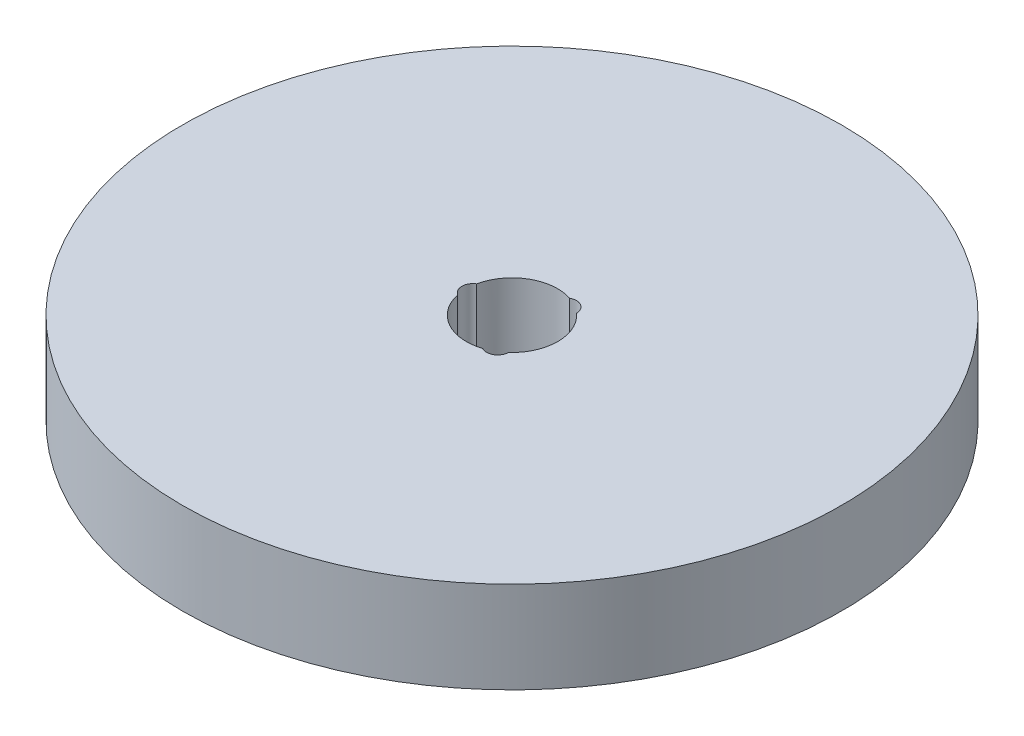
SolidWorks part; units mm, degrees
ref_plane "Front Plane" through (0, 0, 0) normal (0, 0, 1) x (1, 0, 0)
ref_plane "Top Plane" through (0, 0, 0) normal (0, 1, 0) x (1, 0, 0)
ref_plane "Right Plane" through (0, 0, 0) normal (1, 0, 0) x (0, 0, -1)
sketch "Sketch1" plane through (0, 0, 0) normal (0, 1, 0) x (1, 0, 0)
  circle A0 centre (0, 0) radius 90
  dimension "FLANGE_OD" = 180
extrude "Boss-Extrude1" add sketch "Sketch1" along normal blind 25
sketch "Sketch2" plane through (0, 0, 0) normal (0, 1, 0) x (1, 0, 0)
  circle A0 centre (0, 0) radius 12.5
  dimension "BORE_D" = 25
extrude "Cut-Extrude1" cut sketch "Sketch2" along normal through all
sketch "Sketch3" plane through (0, 25, 0) normal (0, 1, 0) x (1, 0, 0)
  circle A0 centre (0, 0) radius 10.6513 construction
  circle A1 centre (-10.6513, 0) radius 3.0361
  dimension "BOLT_D" = 6.0722
  dimension "BOLT_PCD" = 21.3026
extrude "Cut-Extrude2" cut sketch "Sketch3" against normal blind 23.6338
pattern_circular "CirPattern1" count 3 over 360 about axis through (0, 0, 0) along (0, 1, 0) of "Cut-Extrude2"
